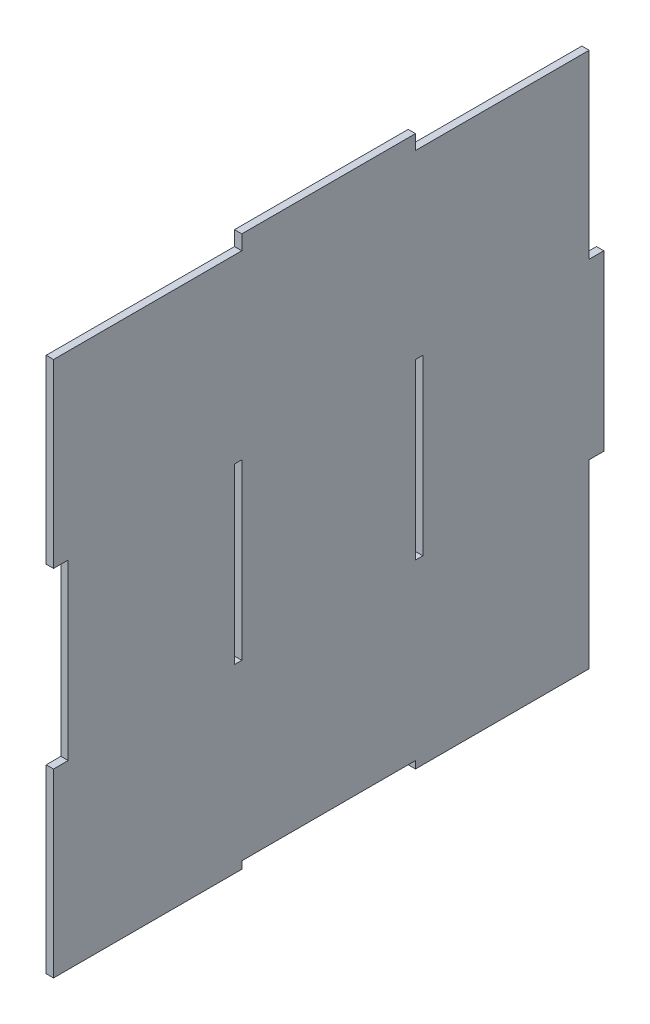
SolidWorks part; units mm, degrees
material "Delrin 2700 NC010, Low Viscosity Acetal Copolymer (SS)"
ref_plane "Front Plane" through (0, 0, 0) normal (0, 0, 1) x (1, 0, 0)
ref_plane "Top Plane" through (0, 0, 0) normal (0, 1, 0) x (1, 0, 0)
ref_plane "Right Plane" through (0, 0, 0) normal (1, 0, 0) x (0, 0, -1)
sketch "Sketch2" plane through (0, 0, 0) normal (1, 0, 0) x (0, 0, -1)
  line L0 (-113, 0) -> (-40.8417, 0)
  line L1 (-37.6667, 119.35) -> (-37.6667, 113)
  line L2 (-37.6667, 0) -> (37.6667, 0)
  line L3 (-37.6667, 119.35) -> (37.6667, 119.35)
  line L4 (119.35, 37.6667) -> (119.35, -37.6667)
  line L5 (-113, 37.6667) -> (-119.35, 37.6667)
  line L6 (-37.6667, 113) -> (37.6667, 113)
  line L7 (0, 119.35) -> (0, 113)
  line L8 (-113, 37.6667) -> (-113, -37.6667)
  line L9 (-113, 0) -> (-119.35, 0)
  line L10 (-37.6667, 116.175) -> (-116.175, 116.175)
  line L11 (-116.175, 116.175) -> (-116.175, 37.6667)
  line L12 (-116.175, 37.6667) -> (-113, 37.6667)
  line L13 (-113, 37.6667) -> (-113, -37.6667)
  line L14 (-40.8417, -37.6667) -> (-40.8417, 37.6667)
  line L15 (-40.8417, 37.6667) -> (-37.6667, 37.6667)
  line L16 (-37.6667, 37.6667) -> (-37.6667, -37.6667)
  line L17 (-119.35, 37.6667) -> (-119.35, -37.6667)
  line L18 (37.6667, 37.6667) -> (37.6667, -37.6667)
  line L19 (40.8417, 37.6667) -> (37.6667, 37.6667)
  line L20 (40.8417, -37.6667) -> (40.8417, 37.6667)
  line L21 (113, 37.6667) -> (113, -37.6667)
  line L22 (116.175, 37.6667) -> (113, 37.6667)
  line L23 (116.175, 116.175) -> (116.175, 37.6667)
  line L24 (0, 119.35) -> (0, -119.35)
  line L25 (37.6667, 116.175) -> (116.175, 116.175)
  line L26 (113, 0) -> (119.35, 0)
  line L27 (113, 37.6667) -> (113, -37.6667)
  line L28 (113, 37.6667) -> (119.35, 37.6667)
  line L29 (37.6667, 119.35) -> (37.6667, 113)
  line L30 (113, 0) -> (40.8417, 0)
  line L31 (37.6667, -119.35) -> (37.6667, -113)
  line L32 (113, -37.6667) -> (119.35, -37.6667)
  line L33 (37.6667, -116.175) -> (116.175, -116.175)
  line L34 (116.175, -116.175) -> (116.175, -37.6667)
  line L35 (116.175, -37.6667) -> (113, -37.6667)
  line L36 (40.8417, -37.6667) -> (37.6667, -37.6667)
  line L37 (-40.8417, -37.6667) -> (-37.6667, -37.6667)
  line L38 (-116.175, -37.6667) -> (-113, -37.6667)
  line L39 (-116.175, -116.175) -> (-116.175, -37.6667)
  line L40 (-37.6667, -116.175) -> (-116.175, -116.175)
  line L41 (0, -119.35) -> (0, -113)
  line L42 (-37.6667, -113) -> (37.6667, -113)
  line L43 (-113, -37.6667) -> (-119.35, -37.6667)
  line L44 (-37.6667, -119.35) -> (37.6667, -119.35)
  line L45 (-37.6667, -119.35) -> (-37.6667, -113)
  point P35 (0, 0)
  point P36 (0, 0)
  dimension "D1" = 3.175
  dimension "D2" = 37.6667
  dimension "D3" = 3.175
  dimension "D4" = 3.175
  dimension "D5" = 75.3333
  dimension "D6" = 75.3333
  dimension "D7" = 113
  dimension "D8" = 37.6667
  dimension "D9" = 113
  dimension "D10" = 3.175
  dimension "D11" = 3.175
  dimension "D13" = 0
  dimension "D14" = 0
extrude "Boss-Extrude1" add sketch "Sketch2" along normal blind 3.175 contours L24 L6 L1 L10 L11 L5 L8 L0 L14 L15 L16 L2 | L29 L3 L7 L6 | L30 L21 L22 L23 L25 L29 L6 L24 L2 L18 L19 L20 | L28 L22 L21 L26 L4 | L21 L32 L4 L26 | L24 L42 L31 L33 L34 L32 L21 L30 L20 L36 L18 L2 | L40 L45 L42 L24 L2 L16 L37 L14 L0 L8 L38 L39 | L6 L29 L3 L1 region at (0, 58.2878, 58.102) region at (0, -58.2878, 58.102) region at (0, 58.2878, -58.102) region at (0, -58.2878, -58.102) region at (0, 116.175, -18.8333) region at (0, -18.8333, -116.175) region at (0, 18.8333, -116.175)
sketch "Sketch3" plane through (3.175, 0, 0) normal (1, 0, 0) x (0, 0, -1)
  line L0 (-37.6667, -116.175) -> (-116.175, -116.175) construction
  line L1 (-116.175, 116.175) -> (-119.35, 116.175)
  line L2 (-116.175, 116.175) -> (-116.175, -116.175)
  line L3 (-116.175, -116.175) -> (-119.35, -116.175)
  line L4 (-119.35, 116.175) -> (-119.35, -116.175)
  line L5 (-116.175, -37.6667) -> (-113, -37.6667) construction
  line L6 (-113, 37.6667) -> (-119.35, 37.6667)
  line L7 (-113, 37.6667) -> (-113, -37.6667)
  line L8 (-113, -37.6667) -> (-119.35, -37.6667)
  line L9 (-119.35, 37.6667) -> (-119.35, -37.6667)
  line L10 (-37.6667, 119.35) -> (37.6667, 119.35) construction
  line L11 (37.6667, 116.175) -> (-37.6667, 116.175)
  line L12 (37.6667, 116.175) -> (37.6667, 122.525)
  line L13 (37.6667, 122.525) -> (-37.6667, 122.525)
  line L14 (-37.6667, 116.175) -> (-37.6667, 122.525)
  line L15 (-37.6667, 119.35) -> (-37.6667, 116.175) construction
  line M5 (37.6667, 119.35) -> (-37.6667, 119.35)
  line M8 (-116.175, 116.175) -> (-116.175, 37.6667)
  line M12 (-116.175, -37.6667) -> (-116.175, -116.175)
  dimension "D1" = 3.175
  dimension "D2" = 0
  dimension "D3" = 0
  dimension "D4" = 3.175
  dimension "D5" = 0
extrude "Boss-Extrude2" add sketch "Sketch3" against normal blind 3.175 contours L6 L1 L4 M8 | L8 L4 L3 M12 | L14 L12 L13 M5 region at (3.175, 76.9208, 117.7625) region at (3.175, -76.9208, 117.7625) region at (3.175, 120.9375, 0)
sketch "Sketch4" plane through (3.175, 0, 0) normal (1, 0, 0) x (0, 0, -1)
  line L0 (37.6667, 116.175) -> (116.175, 116.175) construction
  line L1 (119.35, 37.6667) -> (113, 37.6667)
  line L2 (119.35, 37.6667) -> (119.35, 116.175)
  line L3 (119.35, 116.175) -> (113, 116.175)
  line L4 (113, 37.6667) -> (113, 116.175)
  line L5 (37.6667, -116.175) -> (116.175, -116.175) construction
  line L6 (113, 37.6667) -> (119.35, 37.6667)
  line L7 (113, 37.6667) -> (113, -37.6667)
  line L8 (113, -37.6667) -> (119.35, -37.6667)
  line L9 (119.35, 37.6667) -> (119.35, -37.6667)
  line L10 (119.35, -37.6667) -> (113, -37.6667)
  line L11 (119.35, -37.6667) -> (119.35, -116.175)
  line L12 (119.35, -116.175) -> (113, -116.175)
  line L13 (113, -37.6667) -> (113, -116.175)
  line L14 (116.175, 116.175) -> (116.175, 37.6667) construction
  line L16 (116.175, 116.175) -> (113, 116.175)
  line L17 (116.175, 116.175) -> (116.175, -116.175)
  line L18 (116.175, -116.175) -> (113, -116.175)
  line L19 (113, 116.175) -> (113, -116.175)
  line M13 (37.6667, -116.175) -> (116.175, -116.175)
  line M14 (116.175, -116.175) -> (116.175, -37.6667)
  line M18 (116.175, 37.6667) -> (116.175, 116.175)
  line M19 (116.175, 116.175) -> (37.6667, 116.175)
  dimension "D1" = 3.175
extrude "Cut-Extrude1" cut sketch "Sketch4" against normal blind 3.175 contours L4 L1 M18 M19 | L8 L13 M13 M14 region at (3.175, 76.9208, -114.5875) region at (3.175, -76.9208, -114.5875)
equation "\"D8@Sketch2\"=\"D2@Sketch2\""
equation "\"D11@Sketch2\"=\"D3@Sketch2\""
equation "\"D4@Sketch2\"=\"D3@Sketch2\""
equation "\"D10@Sketch2\"=\"D3@Sketch2\""
equation "\"Resolution Projector X\"= 1920'a_ resolution data"
equation "\"Resolution Projector Y\"= 1080'a_ resolution data"
equation "\"Resolution Build\"= 0.1'a_ resolution data"
equation "\"Size Build Volume X\"= \"Resolution Projector X\" * \"Resolution Build\"'b_ build volume data"
equation "\"Size Build Volume Y\"= 2 * \"Resolution Projector Y\" * \"Resolution Build\"'b_ build volume data"
equation "\"Size Build Volume Z\"= \"Size Build Volume Y\"'b_ build volume data"
equation "\"Size Enclosure Internal X\"= 350mm'c_ size enclosure Internal data"
equation "\"Size Enclosure Internal Y\"= \"Size Enclosure Internal X\"'c_ size enclosure Internal data"
equation "\"Size Enclosure Internal Z\"= \"Size Enclosure Internal X\"'c_ size enclosure Internal data"
equation "\"Size Enclosure External Z\"= 1000mm'c_ size enclosure External data"
equation "\"Clearance Vat\"= 10mm'd_ clearance vat data"
equation "\"Size Vat X\"= \"Size Build Volume X\" + \"Clearance Vat\"'f_ size vat data"
equation "\"Size Vat Y\"= \"Size Build Volume Y\" + \"Clearance Vat\"'f_ size vat data"
equation "\"Size Vat Z\"= \"Size Build Volume Z\" + \"Clearance Vat\"'f_ size vat data"
equation "\"Thickness Vat\"= 3.175mm'g_ thickness vat data"
equation "\"width rib\"= 2 * \"Thickness Vat\"'g_ thickness of the Rib"
equation "\"width Lip on rib\"= \"Thickness Vat\" * 2'g_ thickness of the lip connected to the tab"
equation "\"height Lip on rib\" = \"width Lip on rib\"'g_ height of lip on rib structure"
equation "\"height adjustment\" = \"Thickness Vat\" * 2'g_ height adjustment for lip.  This flushes the top part of the tab to top of the walls"
equation "\"goofy tab x\"= \"Size Vat X\" * ( 1 / 3 ) - \"width rib\"'h_ goofy slot found on rib X"
equation "\"goofy tab y\"= \"Size Vat Y\" * ( 1 / 3 ) - \"width rib\"'h_ goofy slot found on rib Y"
equation "\"D9@Sketch2\"=\"Size Vat Y\"/2mm"
equation "\"D5@Sketch2\"=\"D6@Sketch2\""
equation "\"D1@Sketch2\"=\"D10@Sketch2\""
equation "\"D2@Sketch2\"=\"D7@Sketch2\"/3"
equation "\"D6@Sketch2\"=\"Size Vat Y\"/3"
equation "\"D3@Sketch2\"=\"Thickness Vat\""
equation "\"D7@Sketch2\"=\"Size Vat Z\"/2"
equation "\"D1@Boss-Extrude1\"=\"Thickness Vat\""
equation "\"D1@Sketch3\"=\"Thickness Vat\""
equation "\"D1@Boss-Extrude2\"=\"Thickness Vat\""
equation "\"D1@Sketch4\"=\"Thickness Vat\""
equation "\"D1@Cut-Extrude1\"=\"Thickness Vat\""
equation "\"D4@Sketch3\"=\"Thickness Vat\""
